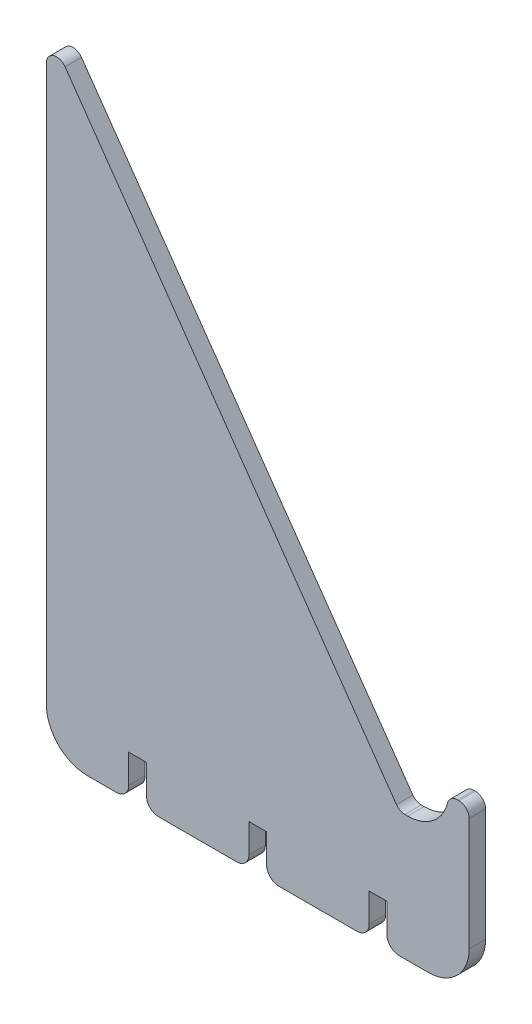
SolidWorks part; units mm, degrees
ref_plane "Front Plane" through (0, 0, 0) normal (0, 0, 1) x (1, 0, 0)
ref_plane "Top Plane" through (0, 0, 0) normal (0, 1, 0) x (1, 0, 0)
ref_plane "Right Plane" through (0, 0, 0) normal (1, 0, 0) x (0, 0, -1)
sketch "Sketch1" plane through (0, 0, 0) normal (0, 0, 1) x (1, 0, 0)
  line L1 (86.4963, -131.1793) -> (85.7977, -131.1793)
  line L2 (83.7498, -130.1133) -> (3.0077, -14.8016)
  line L3 (-0.8175, -9.3387) -> (79.4832, -124.02) construction
  line L4 (98.6297, -121.6843) -> (98.9835, -121.6843)
  line L6 (101.4835, -124.1843) -> (101.4835, -151.6843)
  line L7 (91.4835, -161.6843) -> (8.4598, -161.6843)
  line L8 (-1.5402, -151.6843) -> (-1.5402, -16.2355)
  arc A0 (96.203, -123.5833) -> (86.4963, -131.1793) centre (86.4963, -121.1793) cw
  arc A1 (101.4835, -151.6843) -> (91.4835, -161.6843) centre (91.4835, -151.6843) cw
  arc A2 (8.4598, -161.6843) -> (-1.5402, -151.6843) centre (8.4598, -151.6843) cw
  arc A3 (85.7977, -131.1793) -> (83.7498, -130.1133) centre (85.7977, -128.6793) cw
  arc A4 (98.9835, -121.6843) -> (101.4835, -124.1843) centre (98.9835, -124.1843) cw
  arc A5 (96.203, -123.5833) -> (98.6297, -121.6843) centre (98.6297, -124.1843) cw
  arc A6 (3.0077, -14.8016) -> (-1.5402, -16.2355) centre (0.9598, -16.2355) ccw
  point P8 (96.4963, -131.1793)
  point P14 (101.4835, -161.6843)
  point P17 (0, 0)
  point P19 (84.4963, -131.1793)
  point P22 (101.4835, -121.6843)
  point P25 (96.4835, -121.6843)
  point P28 (-1.5402, -8.3065)
  dimension "D3" = 10
  dimension "D6" = 10
  dimension "D7" = 2.5
  dimension "D8" = 2.5
  dimension "D1" = 150
  dimension "D2" = 12
  dimension "D4" = 40
  dimension "D5" = 5
extrude "Boss-Extrude1" add sketch "Sketch1" along normal blind 4
sketch "Sketch3" plane through (0, 0, 0) normal (0, 0, -1) x (-1, 0, 0)
  line L0 (-8.4598, -161.6843) -> (-91.4835, -161.6843) construction
  line L5 (-52.1217, -161.6843) -> (-52.1217, -151.6843)
  line L10 (-22.8217, -161.6843) -> (-18.5217, -161.6843)
  line L11 (-22.8217, -161.6843) -> (-22.8217, -151.6843)
  line L12 (-22.8217, -151.6843) -> (-18.5217, -151.6843)
  line L13 (-18.5217, -161.6843) -> (-18.5217, -151.6843)
  line L14 (-52.1217, -151.6843) -> (-47.8217, -151.6843)
  line L15 (-47.8217, -161.6843) -> (-47.8217, -151.6843)
  line L16 (-52.1217, -161.6843) -> (-47.8217, -161.6843)
  line L17 (-81.4217, -161.6843) -> (-81.4217, -151.6843)
  line L18 (-81.4217, -151.6843) -> (-77.1217, -151.6843)
  line L19 (-77.1217, -161.6843) -> (-77.1217, -151.6843)
  line L20 (-81.4217, -161.6843) -> (-77.1217, -161.6843)
  line L21 (-81.4217, -156.6843) -> (-101.4835, -156.6843) construction
  line L22 (-18.5217, -156.6843) -> (1.5402, -156.6843) construction
  line L23 (1.5402, -16.2355) -> (1.5402, -151.6843) construction
  line L24 (-101.4835, -151.6843) -> (-101.4835, -124.1843) construction
  line L25 (-77.1217, -156.6843) -> (-52.1217, -156.6843) construction
  line L26 (-52.1217, -156.6843) -> (-47.8217, -156.6843) construction
  line L27 (-47.8217, -156.6843) -> (-22.8217, -156.6843) construction
  point P18 (-19.1412, -171.6843)
  point P31 (-19.1529, -171.6843)
  point P32 (-76.4905, -161.6843)
  point P33 (-80.7905, -181.6843)
  point P34 (-80.7905, -161.6843)
  dimension "D1" = 4.3
  dimension "D2" = 10
  dimension "D4" = 25
  dimension "D3" = 3
extrude "Cut-Extrude1" cut sketch "Sketch3" against normal through all
fillet "Fillet1" radius 3 6 edges at (18.5217, -161.6843, 2) (22.8217, -161.6843, 2) (47.8217, -161.6843, 2) (52.1217, -161.6843, 2) (77.1217, -161.6843, 2) (81.4217, -161.6843, 2)
